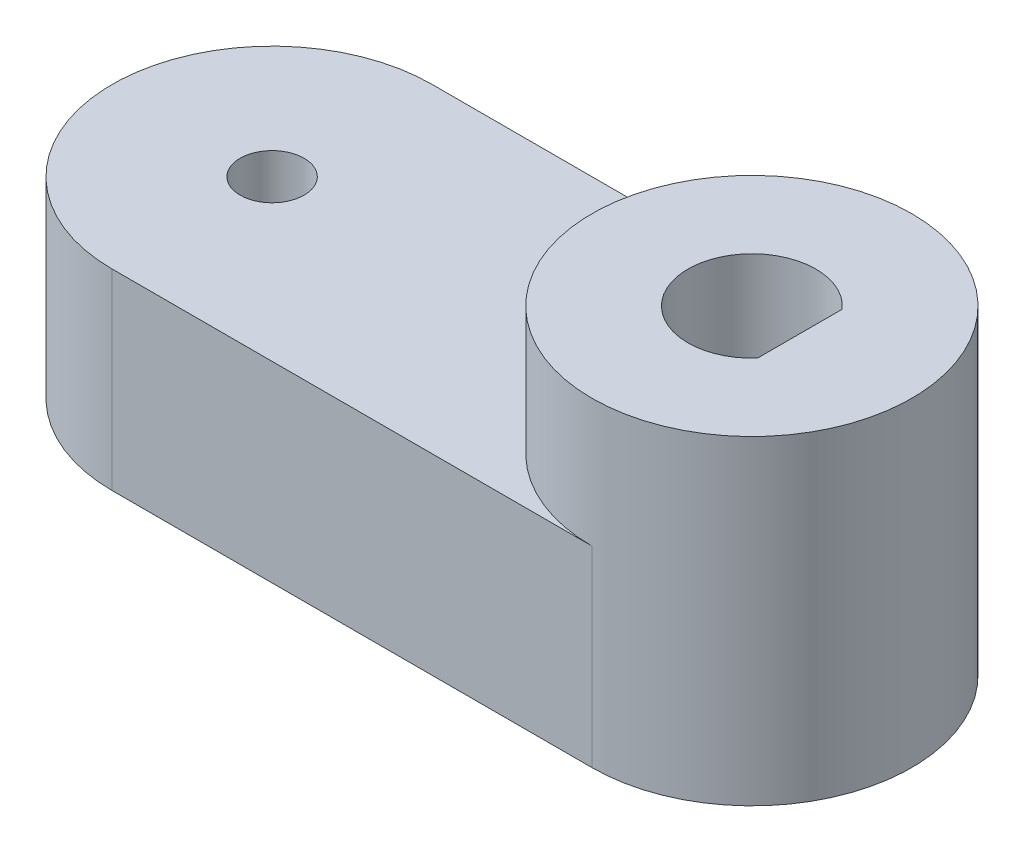
SolidWorks part; units mm, degrees
ref_plane "Front Plane" through (0, 0, 0) normal (0, 0, 1) x (1, 0, 0)
ref_plane "Top Plane" through (0, 0, 0) normal (0, 1, 0) x (1, 0, 0)
ref_plane "Right Plane" through (0, 0, 0) normal (1, 0, 0) x (0, 0, -1)
sketch "Sketch1" plane through (0, 0, 0) normal (0, 1, 0) x (1, 0, 0)
  line L0 (0, 5) -> (15, 5)
  line L1 (0, -5) -> (15, -5)
  arc A0 (0, 5) -> (0, -5) centre (0, 0) ccw
  arc A1 (15, 5) -> (15, -5) centre (15, 0) cw
  circle A2 centre (0, 0) radius 1
  point P8 (-5, 0)
  point P9 (20, 0)
  dimension "D1" = 5
  dimension "D3" = 5
  dimension "D4" = 2
  dimension "D2" = 15
  dimension "D5" = 25
  dimension "D6" = 10
extrude "Boss-Extrude1" add sketch "Sketch1" along normal blind 6
sketch "Sketch2" plane through (0, 6, 0) normal (0, 1, 0) x (1, 0, 0)
  line L0 (15, 5) -> (0, 5) construction
  circle A0 centre (15, 0) radius 5
extrude "Boss-Extrude2" add sketch "Sketch2" along normal blind 4
sketch "Sketch3" plane through (0, 10, 0) normal (0, 1, 0) x (1, 0, 0)
  line L0 (16.5, -1.3229) -> (16.5, 1.3229)
  arc A0 (16.5, 1.3229) -> (16.5, -1.3229) centre (15, 0) ccw
  dimension "D1" = 4
  dimension "D2" = 1.5
extrude "Cut-Extrude1" cut sketch "Sketch3" against normal through all
